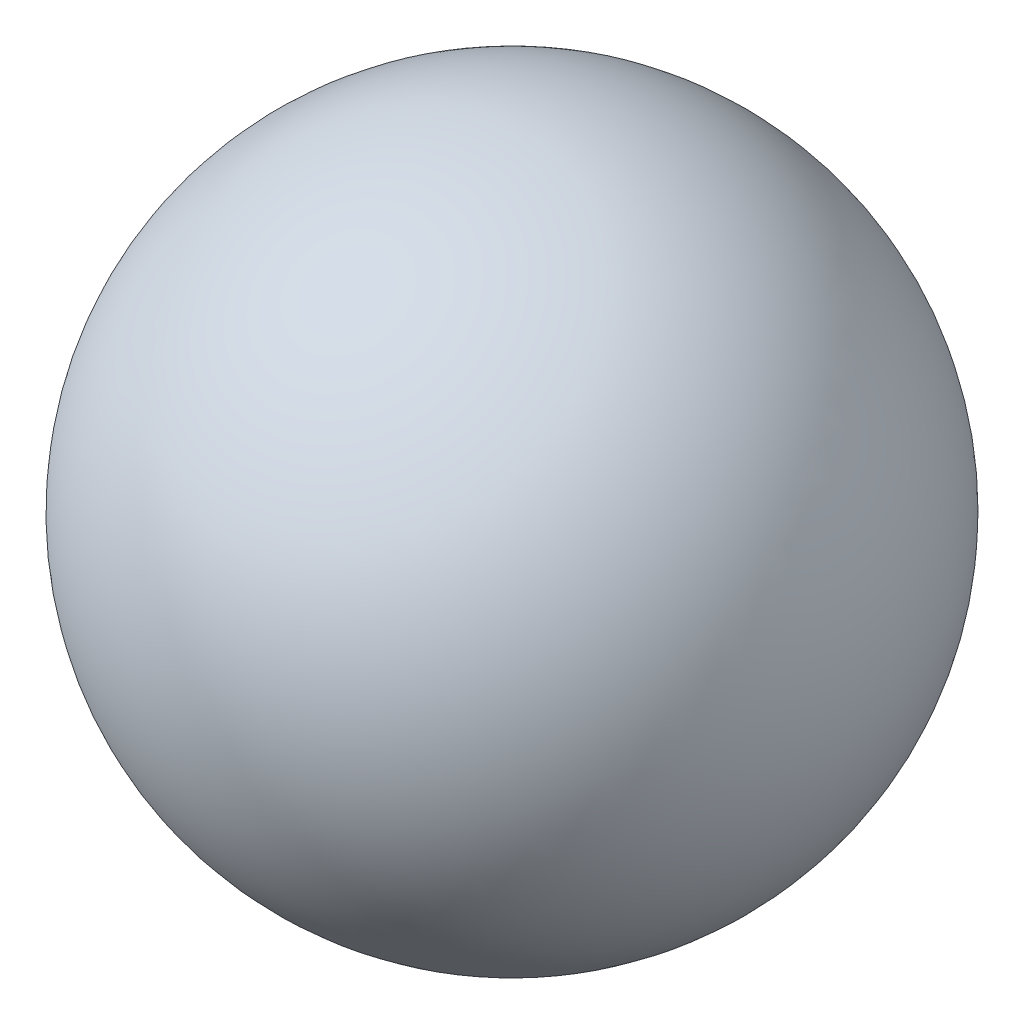
SolidWorks part; units mm, degrees
material "Plain Carbon Steel"
ref_plane "Front Plane" through (0, 0, 0) normal (0, 0, 1) x (1, 0, 0)
ref_plane "Top Plane" through (0, 0, 0) normal (0, 1, 0) x (1, 0, 0)
ref_plane "Right Plane" through (0, 0, 0) normal (1, 0, 0) x (0, 0, -1)
sketch "Sketch1" plane through (0, 0, 0) normal (0, 0, 1) x (1, 0, 0)
  line L0 (0, 5) -> (0, -5)
  arc A0 (0, 5) -> (0, -5) centre (0, 0) cw
  point P7 (0, 0)
  dimension "D1" = 5
revolve "Revolve1" add sketch "Sketch1" angle 360 about L0
sketch "Sketch2" plane through (0, 0, 0) normal (0, 1, 0) x (1, 0, 0)
  circle A0 centre (0, 0) radius 2
  dimension "D1" = 4
extrude "Cut-Extrude1" cut sketch "Sketch2" against normal up to next
extrude "Cut-Extrude2" cut sketch "Sketch2<2>" along normal blind 2.5
sketch "Sketch2<2>" plane through (0, 0, 0) normal (0, 1, 0) x (1, 0, 0) same geometry as "Sketch2"
thread "Thread1" pitch 0.7 method extrude profile "Thread Profile1" start angle 0, offset 0, length 0, pitch 0.7, diameter 4
ref_plane "Plane1" through (2, -4.5826, 0) normal (0, 0, 1) x (1, 0, 0)
sketch "Thread Profile1" plane through (2, -4.5826, 0) normal (0, 0, 1) x (1, 0, 0)
  line L0 (0, 0) -> (0, 0.7) construction
  line L11 (0, 0) -> (0, 0.6125)
  line L12 (0, 0.6125) -> (-0.3789, 0.3937)
  line L13 (-0.3789, 0.3937) -> (-0.3789, 0.2187)
  line L15 (-0.3789, 0.2187) -> (0, 0)
  line L17 (-0.3789, 0.3062) -> (0, 0.3062) construction
  point P2 (0, 0)
  dimension "Pitch" = 0.7
  dimension "Profile_Angle" = 60
  dimension "Profile_Land" = 0.175
  dimension "Profile_Height" = 0.3789
